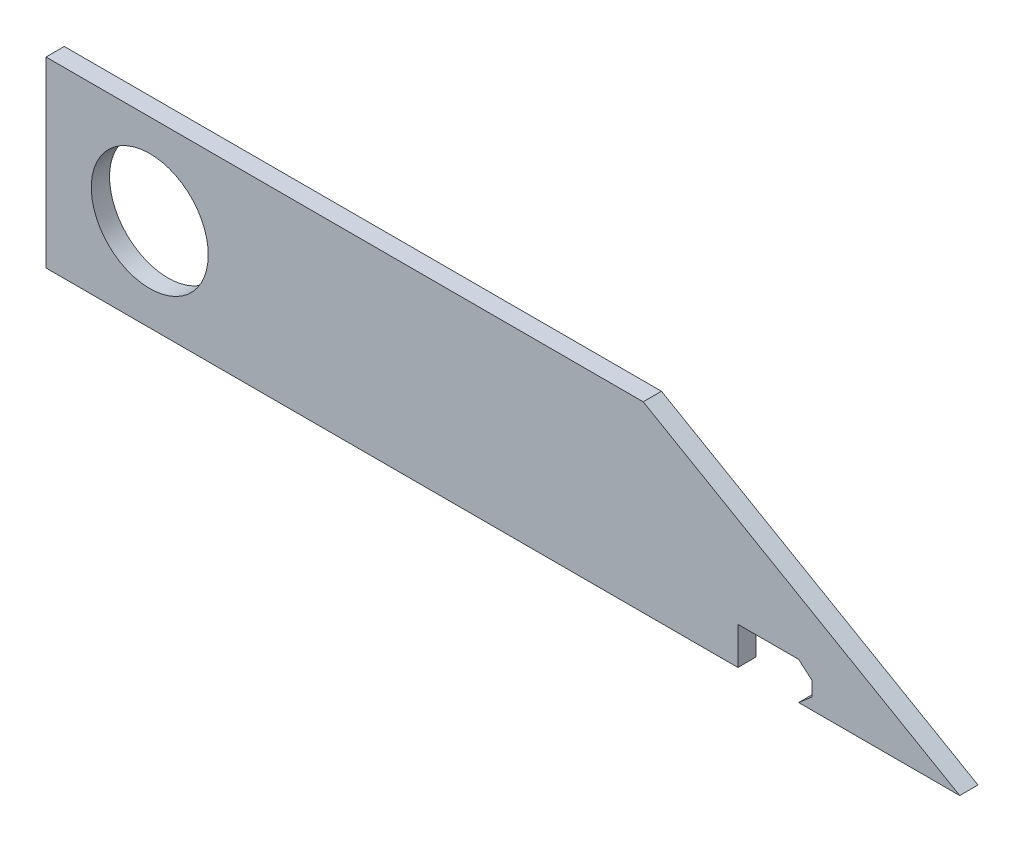
SolidWorks part; units mm, degrees
ref_plane "Front Plane" through (0, 0, 0) normal (0, 0, 1) x (1, 0, 0)
ref_plane "Top Plane" through (0, 0, 0) normal (0, 1, 0) x (1, 0, 0)
ref_plane "Right Plane" through (0, 0, 0) normal (1, 0, 0) x (0, 0, -1)
sketch "Sketch2" plane through (0, 0, 0) normal (0, 0, 1) x (1, 0, 0)
  line L0 (-63.5, 2.4) -> (63.5, 2.4)
  line L1 (63.5, 2.4) -> (19.5059, 27.8)
  line L2 (19.5059, 27.8) -> (-63.5, 27.8)
  line L3 (-63.5, 27.8) -> (-63.5, 2.4)
  dimension "D1" = 25.4
  dimension "D2" = 30
extrude "Boss-Extrude1" add sketch "Sketch2" against normal blind 2.54
sketch "Sketch3" plane through (0, 0, 0) normal (0, 0, 1) x (1, 0, 0)
  circle A0 centre (-49.0783, 15.2636) radius 8.128
extrude "Cut-Extrude1" cut sketch "Sketch3" against normal blind 2.54
sketch "Sketch4" plane through (0, 0, -2.54) normal (0, 0, -1) x (-1, 0, 0)
  line L0 (-41.1054, 7.6) -> (-32.6673, 7.6)
  line L1 (-32.6673, 7.6) -> (-32.6673, 2.4)
  line L2 (63.5, 2.4) -> (-63.5, 2.4) construction
  line L3 (-32.6673, 7.6) -> (-32.6673, 2.4) construction
  line L4 (-32.6673, 2.4) -> (-41.1054, 2.4)
  line L5 (-41.1054, 2.4) -> (-42.9673, 4) construction
  line L6 (-41.1054, 2.4) -> (-42.9673, 4)
  line L7 (-42.9673, 4) -> (-42.9673, 6)
  line L8 (-42.9673, 6) -> (-41.1054, 7.6) construction
  line L9 (-42.9673, 4) -> (-42.9673, 6) construction
  line L10 (-42.9673, 6) -> (-41.1054, 7.6)
extrude "Cut-Extrude2" cut sketch "Sketch4" against normal through all
